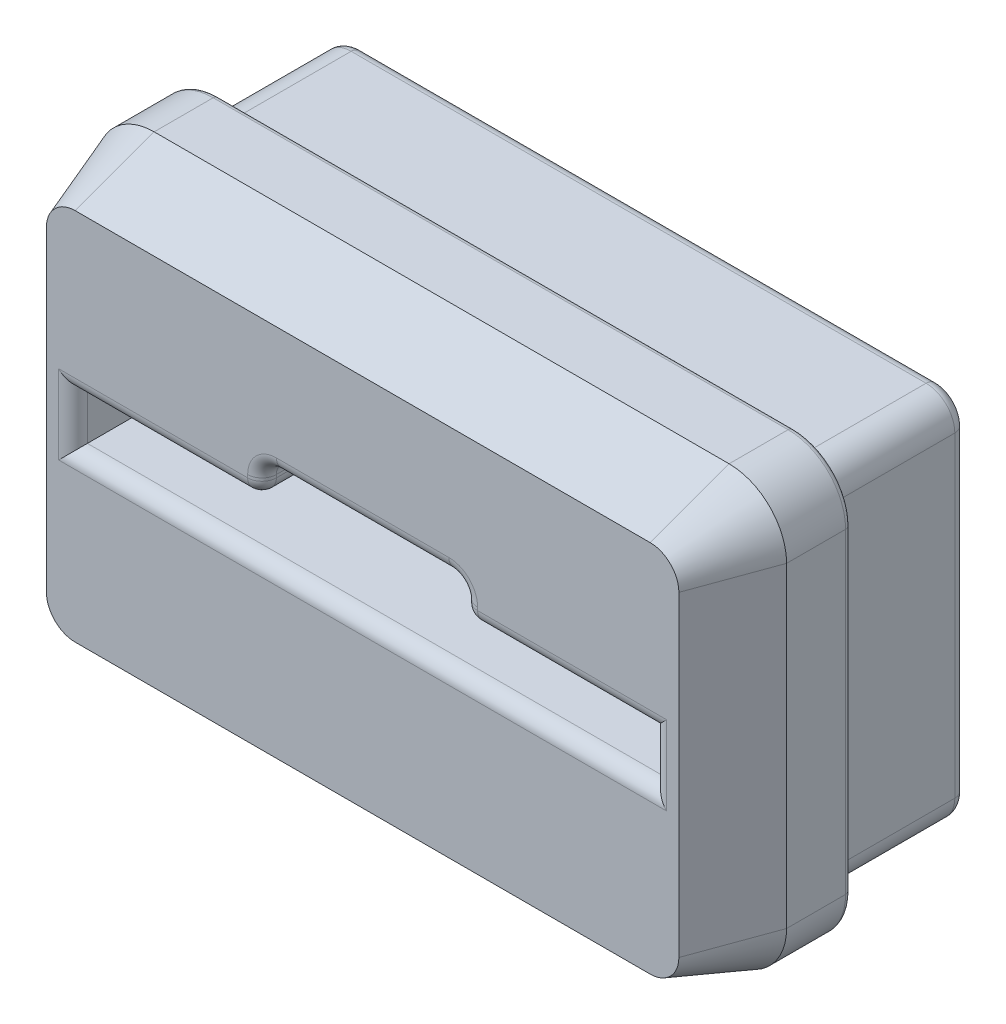
SolidWorks part; units mm, degrees
ref_plane "Front Plane" through (0, 0, 0) normal (0, 0, 1) x (1, 0, 0)
ref_plane "Top Plane" through (0, 0, 0) normal (0, 1, 0) x (1, 0, 0)
ref_plane "Right Plane" through (0, 0, 0) normal (1, 0, 0) x (0, 0, -1)
sketch "Sketch1" plane through (0, 0, 0) normal (0, 1, 0) x (1, 0, 0)
  line L1 (-12, 6.5) -> (12, 6.5)
  line L2 (-12, 6.5) -> (-12, -6.5)
  line L3 (-12, -6.5) -> (12, -6.5)
  line L4 (12, 6.5) -> (12, -6.5)
  line L5 (-12, 6.5) -> (12, -6.5) construction
  line L6 (-12, -6.5) -> (12, 6.5) construction
  point P0 (0, 0)
  dimension "D1" = 24
  dimension "D2" = 13
extrude "Boss-Extrude1" add sketch "Sketch1" along normal blind 15
sketch "Sketch2" plane through (0, 0, 6.5) normal (0, 0, 1) x (1, 0, 0)
  line L0 (0, 0) -> (0, 15) construction
  line L1 (-12, 15) -> (12, 15) construction
  line L2 (-12, 0) -> (12, 0) construction
  line L3 (-10.075, 8.45) -> (10.075, 8.45)
  line L4 (-10.075, 8.45) -> (-10.075, 6.7)
  line L5 (-10.075, 6.7) -> (10.075, 6.7)
  line L6 (10.075, 8.45) -> (10.075, 6.7)
  line L7 (-10.075, 8.45) -> (10.075, 6.7) construction
  line L8 (-10.075, 6.7) -> (10.075, 8.45) construction
  point P5 (0, 7.575)
  dimension "D1" = 6.7
  dimension "D2" = 1.75
  dimension "D3" = 20.15
extrude "Cut-Extrude1" cut sketch "Sketch2" against normal blind 15
fillet "Fillet1" radius 2 4 edges at (12, 15, 0) (12, 0, 0) (-12, 0, 0) (-12, 15, 0)
chamfer "Chamfer2" distance 1 angle 70 8 edges at (0, 0, 6.5) (-11.4142, 0.5858, 6.5) (11.4142, 0.5858, 6.5) (-12, 7.5, 6.5) (12, 7.5, 6.5) (-11.4142, 14.4142, 6.5) (11.4142, 14.4142, 6.5) (0, 15, 6.5) first distance on face at (0, 7.575, 6.5)
fillet "Fillet2" radius 0.5 4 edges at (10.075, 7.575, 6.5) (0, 8.45, 6.5) (-10.075, 7.575, 6.5) (0, 6.7, 6.5)
sketch "Sketch4" plane through (0, 0, -6.5) normal (0, 0, -1) x (-1, 0, 0)
  line L0 (-10.075, 8.45) -> (-8.575, 8.45)
  line L1 (-10.075, 6.7) -> (10.075, 6.7)
  line L2 (-10.075, 6.7) -> (-10.075, 8.45)
  line L3 (-8.575, 11.8912) -> (8.575, 11.8912)
  line L4 (10.075, 6.7) -> (10.075, 8.45)
  line L5 (-10.075, 8.45) -> (10.075, 8.45) construction
  line L6 (-8.575, 8.45) -> (-8.575, 11.8912)
  line L7 (10.075, 8.45) -> (8.575, 8.45)
  line L8 (8.575, 8.45) -> (8.575, 11.8912)
  dimension "D2" = 1.5
  dimension "D3" = 1.5
extrude "Cut-Extrude4" cut sketch "Sketch4" against normal blind 11
sketch "Sketch5" plane through (0, 0, -6.5) normal (0, 0, -1) x (-1, 0, 0)
  line L5 (-13.5112, 17.4159) -> (13.3444, 17.4159)
  line L6 (-13.5112, 17.4159) -> (-13.5112, -1.8918)
  line L7 (-13.5112, -1.8918) -> (13.3444, -1.8918)
  line L8 (10, 14) -> (-10, 14)
  line L9 (-11, 13) -> (-11, 2)
  line L10 (-10, 1) -> (10, 1)
  line L11 (11, 2) -> (11, 13)
  line L12 (10, 14) -> (-10, 14)
  line L13 (-11, 13) -> (-11, 2)
  line L14 (-10, 1) -> (10, 1)
  line L15 (11, 2) -> (11, 13)
  line L16 (13.3444, 17.4159) -> (13.3444, -1.8918)
  arc A8 (-10, 14) -> (-11, 13) centre (-10, 13) ccw
  arc A9 (-11, 2) -> (-10, 1) centre (-10, 2) ccw
  arc A10 (10, 1) -> (11, 2) centre (10, 2) ccw
  arc A11 (11, 13) -> (10, 14) centre (10, 13) ccw
  arc A12 (-10, 14) -> (-11, 13) centre (-10, 13) ccw
  arc A13 (-11, 2) -> (-10, 1) centre (-10, 2) ccw
  arc A14 (10, 1) -> (11, 2) centre (10, 2) ccw
  arc A15 (11, 13) -> (10, 14) centre (10, 13) ccw
  dimension "D1" = 1
extrude "Cut-Extrude5" cut sketch "Sketch5" against normal blind 8
sketch "Sketch6" plane through (0, 0, -6.5) normal (0, 0, -1) x (-1, 0, 0)
  line L8 (-9, 5.7) -> (9, 5.7)
  line L9 (10.075, 6.7) -> (-10.075, 6.7) construction
  line L12 (10, 13) -> (-10, 13)
  line L13 (-10, 13) -> (-10, 2)
  line L14 (-10, 2) -> (10, 2)
  line L15 (10, 2) -> (10, 13)
  line L17 (-10, 4.7) -> (-10, 3)
  line L18 (-9, 2) -> (9, 2)
  line L19 (10, 3) -> (10, 4.7)
  arc A8 (9, 2) -> (10, 3) centre (9, 3) ccw
  arc A9 (9, 5.7) -> (10, 4.7) centre (9, 4.7) cw
  arc A10 (-10, 3) -> (-9, 2) centre (-9, 3) ccw
  arc A11 (-9, 5.7) -> (-10, 4.7) centre (-9, 4.7) ccw
  dimension "D3" = 1
  dimension "D2" = 1
  dimension "D1" = 1
extrude "Cut-Extrude6" cut sketch "Sketch6" against normal blind 11
sketch "Sketch7" plane through (0, 0, -6.5) normal (0, 0, -1) x (-1, 0, 0)
  line L1 (-14.3755, 18.0591) -> (15.6072, 18.0591)
  line L2 (-14.3755, 18.0591) -> (-14.3755, -3.4999)
  line L3 (-14.3755, -3.4999) -> (15.6072, -3.4999)
  line L4 (15.6072, 18.0591) -> (15.6072, -3.4999)
extrude "Cut-Extrude7" cut sketch "Sketch7" against normal blind 3
chamfer "Chamfer3" distance 2 angle 45 2 edges at (9.325, 8.45, -3.5) (-9.325, 8.45, -3.5)
fillet "Fillet3" radius 0.4 22 edges at (-9.7071, 5.4071, -3.5) (0, 5.7, -3.5) (9.7071, 5.4071, -3.5) (10, 3.85, -3.5) (9.7071, 2.2929, -3.5) (0, 2, -3.5) (-9.7071, 2.2929, -3.5) (10.7071, 13.7071, -3.5) (11, 7.5, -3.5) (10.7071, 1.2929, -3.5) (0, 1, -3.5) (-10.7071, 1.2929, -3.5) (-11, 7.5, -3.5) (-10.7071, 13.7071, -3.5) (9.325, 10.45, -3.5) (8.575, 11.1706, -3.5) (-9.325, 10.45, -3.5) (-8.575, 11.1706, -3.5) (0, 11.8912, -3.5) (0, 6.7, -3.5) (-10, 3.85, -3.5) (0, 14, -3.5)
fillet "Fillet4" radius 0.2 8 edges at (0, 15, 1.5) (11.4142, 14.4142, 1.5) (12, 7.5, 1.5) (11.4142, 0.5858, 1.5) (0, 0, 1.5) (-11.4142, 0.5858, 1.5) (-12, 7.5, 1.5) (-11.4142, 14.4142, 1.5)
sketch "Sketch8" plane through (0, 0, 4.5) normal (0, 0, -1) x (-1, 0, 0)
  line L0 (8.575, 8.45) -> (-8.575, 8.45) construction
  line L1 (-3.5, 9.55) -> (3.5, 9.55)
  line L2 (-3.5, 9.55) -> (-3.5, 7.35)
  line L3 (-3.5, 7.35) -> (3.5, 7.35)
  line L4 (3.5, 9.55) -> (3.5, 7.35)
  line L5 (-3.5, 9.55) -> (3.5, 7.35) construction
  line L6 (-3.5, 7.35) -> (3.5, 9.55) construction
  point P0 (0, 8.45)
  dimension "D1" = 2.2
  dimension "D2" = 7
extrude "Cut-Extrude8" cut sketch "Sketch8" against normal through all
fillet "Fillet5" radius 0.5 9 edges at (3.5, 8.45, 5.25) (3.5, 8.5964, 6.3536) (3.5, 9.25, 6.5) (0, 9.55, 6.5) (-3.5, 9.25, 6.5) (-3.5, 8.45, 5.25) (-3.5, 8.5964, 6.3536) (-3.5, 9.55, 5.5) (3.5, 9.55, 5.5)
